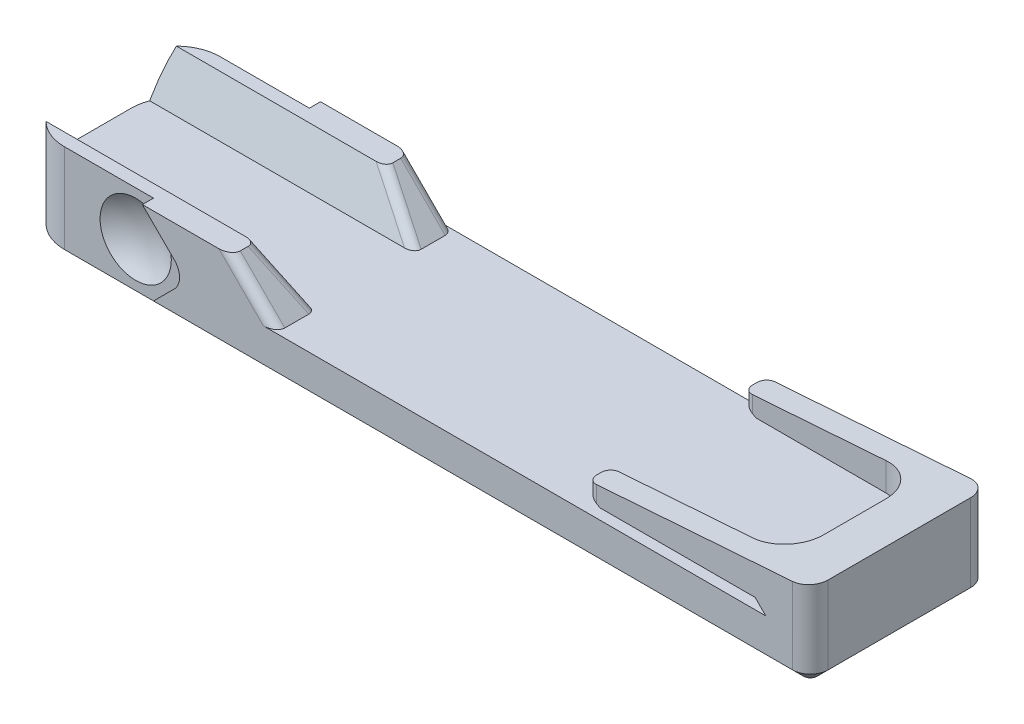
SolidWorks part; units mm, degrees
ref_plane "Front Plane" through (0, 0, 0) normal (0, 0, 1) x (1, 0, 0)
ref_plane "Top Plane" through (0, 0, 0) normal (0, 1, 0) x (1, 0, 0)
ref_plane "Right Plane" through (0, 0, 0) normal (1, 0, 0) x (0, 0, -1)
sketch "Sketch1" plane through (0, 0, 0) normal (0, 1, 0) x (1, 0, 0)
  line L0 (-50.8, 12.7) -> (-57.15, 12.7)
  line L1 (-50.8, -12.7) -> (54.61, -12.7)
  line L2 (-57.15, -6.35) -> (-57.15, 6.35)
  line L3 (-50.8, 12.7) -> (54.61, 12.7)
  line L4 (57.15, -10.16) -> (57.15, 10.16)
  line L5 (-57.15, -12.7) -> (57.15, 12.7) construction
  line L6 (-57.15, 12.7) -> (57.15, -12.7) construction
  line L7 (-57.15, 12.7) -> (-57.15, 6.35)
  line L8 (-57.15, -6.35) -> (-57.15, -12.7)
  line L9 (-57.15, -12.7) -> (-50.8, -12.7)
  arc A2 (54.61, -12.7) -> (57.15, -10.16) centre (54.61, -10.16) ccw
  arc A3 (54.61, 12.7) -> (57.15, 10.16) centre (54.61, 10.16) cw
  point P0 (0, 0)
  dimension "D4" = 2.54
  dimension "D1" = 25.4
  dimension "D2" = 114.3
extrude "Boss-Extrude1" add sketch "Sketch1" along normal blind 12.7
sketch "Sketch2" plane through (-57.15, 0, 0) normal (-1, 0, 0) x (0, 0, 1)
  line L0 (-12.7, 6.35) -> (12.7, 6.35) construction
  line L1 (0, 0) -> (0, 12.7) construction
  line L2 (-12.7, 0) -> (12.7, 0) construction
  line L5 (-9.525, 6.35) -> (-9.525, 12.7)
  line L12 (-9.525, 6.35) -> (9.525, 6.35)
  line L13 (-12.7, 12.7) -> (-12.7, 0) construction
  line L14 (12.7, 12.7) -> (12.7, 0) construction
  line L15 (-9.525, 12.7) -> (9.525, 12.7)
  line L17 (9.525, 12.7) -> (9.525, 6.35)
  line L18 (-12.7, 12.7) -> (12.7, 12.7) construction
  point P16 (0, 6.35)
  dimension "D2" = 19.05
  dimension "D1" = 9.525
extrude "Cut-Extrude1" cut sketch "Sketch2" against normal blind 107.95
sketch "Sketch3" plane through (0, 0, 12.7) normal (0, 0, 1) x (1, 0, 0)
  line L0 (-57.15, 12.7) -> (-57.15, 0) construction
  line L1 (-57.15, 6.35) -> (57.15, 6.35) construction
  line L2 (57.15, 12.7) -> (57.15, 0) construction
  line L3 (-25.4, 12.7) -> (-25.4, 0) construction
  line L4 (25.4, 10.414) -> (57.15, 12.7)
  line L6 (-57.15, 12.7) -> (54.61, 12.7) construction
  line L7 (-57.15, 0) -> (54.61, 0) construction
  line L8 (-25.4, 12.7) -> (-19.05, 6.35)
  line L9 (-19.05, 6.35) -> (50.8, 6.35)
  line L10 (50.8, 6.35) -> (50.8, 7.874)
  line L11 (50.8, 7.874) -> (27.1598, 7.874)
  line L12 (25.4, 8.89) -> (25.4, 10.414)
  line L15 (57.15, 12.7) -> (-25.4, 12.7)
  line L16 (25.4, 8.89) -> (27.1598, 7.874)
  dimension "D1" = 31.75
  dimension "D2" = 45
  dimension "D3" = 1.524
  dimension "D4" = 2.286
  dimension "D5" = 31.75
  dimension "D6" = 6.35
  dimension "D7" = 30
  dimension "D8" = 1.524
extrude "Cut-Extrude2" cut sketch "Sketch3" against normal through all
chamfer "Chamfer1" distance 2.54 angle 70 2 edges at (-38.1, 6.35, 9.525) (-38.1, 6.35, -9.525)
sketch "Sketch4" plane through (0, 0, 12.7) normal (0, 0, 1) x (1, 0, 0)
  line L1 (-57.15, 12.7) -> (-57.15, 0)
  line L7 (-57.15, 0) -> (-38.1, 0)
  line L8 (-57.15, 0) -> (54.61, 0) construction
  line L9 (-38.1, 0) -> (-33.5461, 4.5539)
  line L10 (-33.5461, 8.1461) -> (-38.1, 12.7)
  line L11 (-57.15, 12.7) -> (-25.4, 12.7) construction
  line L12 (-38.1, 12.7) -> (-57.15, 12.7)
  arc A1 (-33.5461, 4.5539) -> (-33.5461, 8.1461) centre (-35.3421, 6.35) ccw
  point P12 (-31.75, 6.35)
  dimension "D4" = 2.54
  dimension "D1" = 45
  dimension "D2" = 45
  dimension "D3" = 25.4
extrude "Cut-Extrude3" cut sketch "Sketch4" against normal blind 1.5875
ref_plane "Plane1" through (-40.64, 0, 0) normal (-1, 0, 0) x (0, 0, 1)
sketch "Sketch6" plane through (-40.64, 0, 0) normal (-1, 0, 0) x (0, 0, 1)
  line L0 (12.7, 6.35) -> (3.745, 6.35) construction
  line L2 (11.1125, 6.35) -> (11.1125, 11.43)
  line L4 (11.1125, 6.35) -> (9.525, 6.35)
  line L5 (-6.985, 6.35) -> (6.985, 6.35) construction
  line L6 (11.1125, 12.7) -> (11.1125, 0) construction
  arc A0 (11.1125, 11.43) -> (9.525, 6.35) centre (18.4467, 6.35) ccw
  dimension "D3" = 8.9217
  dimension "D1" = 5.08
  dimension "D2" = 1.5875
revolve "Cut-Revolve1" cut sketch "Sketch6" angle 360 about L0
ref_plane "Plane2" through (0, 0, 0) normal (0, 0, -1) x (-1, 0, 0)
mirror "Mirror1" about plane through (0, 0, 0) normal (0, 0, -1) of "Cut-Revolve1", "Cut-Extrude3"
chamfer "Chamfer3" distance 1.5875 angle 45 5 edges at (8.255, 0, 12.7) (56.4061, 0, 11.9561) (57.15, 0, 0) (56.4061, 0, -11.9561) (8.255, 0, -12.7)
fillet "Fillet1" radius 6.35 2 edges at (-57.15, 6.35, -11.1125) (-57.15, 6.35, 11.1125)
fillet "Fillet2" radius 1.27 8 edges at (25.4, 9.652, 12.7) (25.4, 9.652, 9.525) (25.4, 9.652, -9.525) (25.4, 9.652, -12.7) (-22.225, 9.525, -12.7) (-22.225, 9.525, -8.1406) (-22.225, 9.525, 8.1406) (-22.225, 9.525, 12.7)
fillet "Fillet3" radius 5.08 2 edges at (50.8, 10.0584, 9.525) (50.8, 10.0584, -9.525)
chamfer "Chamfer4" distance 1.524 angle 45 2 edges at (50.8, 7.874, -8.5725) (50.8, 7.874, 8.5725)
